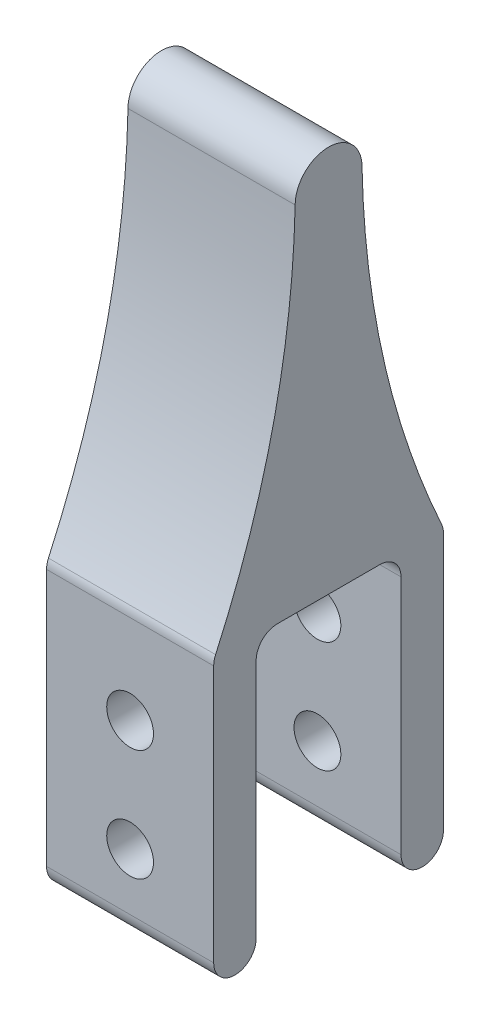
SolidWorks part; units mm, degrees
ref_plane "Front Plane" through (0, 0, 0) normal (0, 0, 1) x (1, 0, 0)
ref_plane "Top Plane" through (0, 0, 0) normal (0, 1, 0) x (1, 0, 0)
ref_plane "Right Plane" through (0, 0, 0) normal (1, 0, 0) x (0, 0, -1)
sketch "Sketch1" plane through (0, 0, 0) normal (1, 0, 0) x (0, 0, -1)
  line L0 (-6.5, 0) -> (-10.31, 0)
  line L1 (-10.31, 0) -> (-10.31, 25.4)
  line L2 (0, -1000) -> (0, 49000) construction
  line L3 (-10.31, 25.4) -> (10.31, 25.4) construction
  line L4 (-6.5, 0) -> (-6.5, 25.4)
  line L5 (-6.5, 25.4) -> (6.5, 25.4)
  line L6 (6.5, 0) -> (6.5, 25.4)
  line L7 (10.31, 0) -> (10.31, 25.4)
  line L8 (6.5, 0) -> (10.31, 0)
  arc A0 (3, 57.15) -> (-3, 57.15) centre (0, 57.15) ccw
  spline S0 degree 2 poles (-10.31, 25.4) (-3.3681, 40.4224) (-3, 57.15) knots 0 0 0 1 1 1
  spline S1 degree 2 poles (10.31, 25.4) (3.3681, 40.4224) (3, 57.15) knots 0 0 0 1 1 1
  point P10 (0, 25.4)
  point P12 (0, 25.4)
  dimension "D5" = 6
  dimension "D1" = 6.5
  dimension "D2" = 3.81
  dimension "D3" = 25.4
  dimension "D4" = 31.75
  dimension "D6" = 25.4
extrude "Boss-Extrude1" add sketch "Sketch1" along normal blind 15
sketch "Sketch2" plane through (0, 0, -10.31) normal (0, 0, -1) x (-1, 0, 0)
  line L0 (-7.5, -974.6) -> (-7.5, 49025.4) construction
  line L1 (-15, 25.4) -> (0, 25.4) construction
  line L2 (-15, 0) -> (0, 0) construction
  circle A0 centre (-7.5, 7) radius 2.1
  circle A1 centre (-7.5, 17) radius 2.1
  point P5 (-7.5, 25.4)
  dimension "D2" = 4.2
  dimension "D3" = 4.2
  dimension "D1" = 10
  dimension "D4" = 7
extrude "Cut-Extrude1" cut sketch "Sketch2" against normal through all
fillet "Fillet2" radius 1.905 8 edges at (7.5, 25.4, -10.31) (7.5, 0, -10.31) (7.5, 0, -6.5) (7.5, 0, 6.5) (7.5, 0, 10.31) (7.5, 25.4, -6.5) (7.5, 25.4, 6.5) (7.5, 25.4, 10.31)
